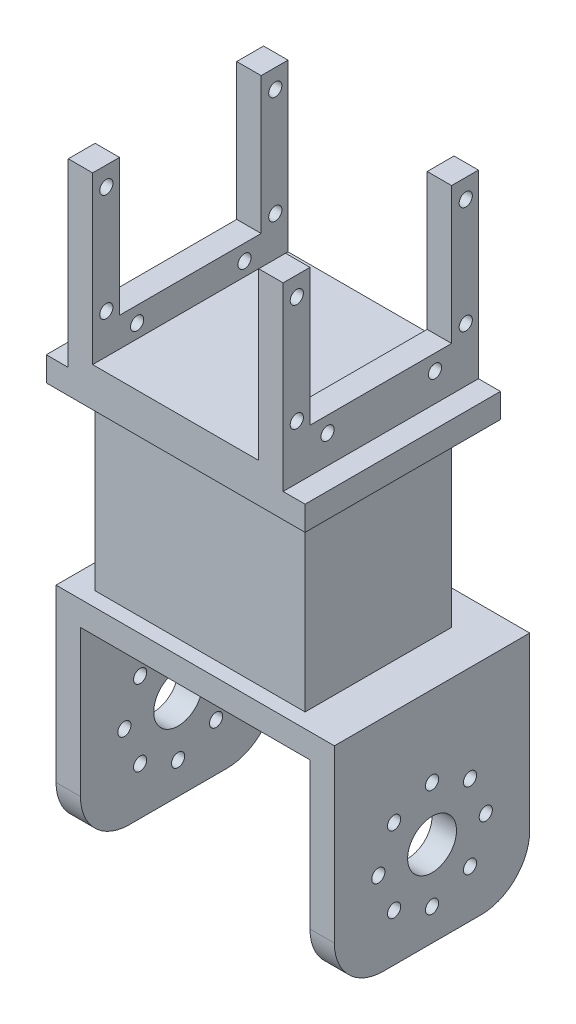
SolidWorks part; units mm, degrees
note: The reader was unsure of these and kept them because the rebuilt part matched: shared geometry of "Sketch8<3>".
material "Aluminium 1050"
ref_plane "Front Plane" through (0, 0, 0) normal (0, 0, 1) x (1, 0, 0)
ref_plane "Top Plane" through (0, 0, 0) normal (0, 1, 0) x (1, 0, 0)
ref_plane "Right Plane" through (0, 0, 0) normal (1, 0, 0) x (0, 0, -1)
sketch "Sketch2" plane through (0, 0, 0) normal (0, 1, 0) x (1, 0, 0)
  line L0 (0, 0) -> (34, 0)
  line L1 (34, 0) -> (34, 40)
  line L2 (34, 40) -> (0, 40)
  line L3 (0, 40) -> (0, 0)
  dimension "D1" = 34
  dimension "D2" = 40
extrude "Boss-Extrude1" add sketch "Sketch2" along normal blind 3
sketch "Sketch3" plane through (0, 0, 0) normal (0, 1, 0) x (1, 0, 0)
  line L0 (0, 0) -> (-5, 0)
  line L1 (-5, 0) -> (-5, 40)
  line L2 (-5, 40) -> (0, 40)
  line L3 (0, 40) -> (0, 0)
  line L4 (17, 40) -> (17, 0) construction
  line L5 (34, 40) -> (0, 40) construction
  line L6 (0, 0) -> (34, 0) construction
  line L7 (34, 40) -> (34, 0)
  line L8 (39, 40) -> (34, 40)
  line L9 (39, 0) -> (39, 40)
  line L10 (34, 0) -> (39, 0)
  dimension "D1" = 5
extrude "Boss-Extrude2" add sketch "Sketch3" along normal blind 37
sketch "Sketch4" plane through (-5, 0, 0) normal (-1, 0, 0) x (0, 0, 1)
  line L0 (-20, 37) -> (-20, 0) construction
  line L1 (-40, 37) -> (0, 37) construction
  line L2 (-40, 0) -> (0, 0) construction
  line L4 (-34.5, 9) -> (-5.5, 9)
  line L11 (-34.5, 37) -> (-34.5, 9)
  line L12 (-5.5, 37) -> (-5.5, 9)
  line L13 (-34.5, 37) -> (-5.5, 37)
  line L14 (-34.5, 37) -> (-34.5, 0) construction
  line L15 (-5.5, 37) -> (-5.5, 0) construction
  circle A2 centre (-2.8, 33.1) radius 1.35
  circle A3 centre (-2.8, 11.1) radius 1.35
  circle A4 centre (-9.1, 5.8) radius 1.35
  circle A5 centre (-37.4, 11.1) radius 1.35
  circle A6 centre (-31.1, 5.8) radius 1.35
  circle A7 centre (-37.4, 33.1) radius 1.35
  dimension "D1" = 2.7
  dimension "D2" = 2.7
  dimension "D3" = 2.7
  dimension "D4" = 2.7
  dimension "D5" = 2.7
  dimension "D6" = 2.7
  dimension "D7" = 14.5
  dimension "D8" = 14.5
  dimension "D9" = 28
extrude "Cut-Extrude1" cut sketch "Sketch4" against normal up to surface (44 mm away) up to face at (39, 18.5, -20)
sketch "Sketch5" plane through (0, 0, 0) normal (0, -1, 0) x (-1, 0, 0)
  line L0 (-17, 0) -> (-17, 40) construction
  line L1 (5, 0) -> (-39, 0) construction
  line L2 (-39, 40) -> (5, 40) construction
  line L3 (9.5, 0) -> (-43.5, 0)
  line L4 (-43.5, 0) -> (-43.5, 40)
  line L5 (-43.5, 40) -> (9.5, 40)
  line L6 (9.5, 0) -> (9.5, 40)
  dimension "D1" = 26.5
extrude "Boss-Extrude3" add sketch "Sketch5" along normal blind 5 contours L5 L6 L3 L4
sketch "Sketch6" plane through (0, -5, 0) normal (0, -1, 0) x (1, 0, 0)
  line L0 (-9.5, 0) -> (43.5, 0)
  line L1 (43.5, 0) -> (43.5, -40)
  line L2 (43.5, -40) -> (-9.5, -40)
  line L3 (-9.5, -40) -> (-9.5, 0)
  line L4 (-4.5, -35) -> (-4.5, -5)
  line L5 (-4.5, -5) -> (38.5, -5)
  line L6 (38.5, -5) -> (38.5, -35)
  line L7 (38.5, -35) -> (-4.5, -35)
  dimension "D1" = 5
extrude "Boss-Extrude4" add sketch "Sketch6" along normal blind 36.85 contours L4 L5 L6 L7
sketch "Sketch7" plane through (0, -41.85, 0) normal (0, -1, 0) x (1, 0, 0)
  line L0 (-7.5, -2) -> (45.5, -2)
  line L1 (45.5, -2) -> (45.5, -42)
  line L2 (45.5, -42) -> (-7.5, -42)
  line L3 (-7.5, -42) -> (-7.5, -2)
  line L4 (-4.5, -5) -> (38.5, -5) construction
  line L5 (-4.5, -35) -> (-4.5, -5) construction
  dimension "D1" = 40
  dimension "D2" = 53
  dimension "D3" = 3
  dimension "D4" = 3
extrude "Boss-Extrude5" add sketch "Sketch7" along normal blind 5
sketch "Sketch8" plane through (0, -46.85, 0) normal (0, -1, 0) x (1, 0, 0)
  line L0 (19, -2) -> (19, -42)
  line L1 (45.5, -2) -> (-7.5, -2) construction
  line L2 (-7.5, -42) -> (45.5, -42) construction
  line L3 (-4.5, -2) -> (-4.5, -42)
  line L4 (42.5, -2) -> (42.5, -42)
  line L5 (-9.5, -2) -> (-9.5, -42)
  line L6 (47.5, -2) -> (47.5, -42)
  line L7 (-9.5, -2) -> (-4.5, -2)
  line L8 (42.5, -2) -> (47.5, -2)
  line L9 (47.5, -42) -> (42.5, -42)
  line L10 (-4.5, -42) -> (-9.5, -42)
  line M1 (-7.5, -2) -> (-7.5, -42)
  line M2 (-7.5, -42) -> (45.5, -42)
  line M3 (45.5, -42) -> (45.5, -2)
  line M4 (45.5, -2) -> (-7.5, -2)
  dimension "D1" = 23.5
  dimension "D2" = 23.5
  dimension "D3" = 28.5
  dimension "D4" = 28.5
extrude "Boss-Extrude6" add sketch "Sketch8" along normal blind 40 contours L10 L7 L5 M1 | L3 M4 M1 M2 | L9 L6 L8 M3
extrude "Boss-Extrude7" add sketch "Sketch8<3>" against normal up to surface (5 mm away) contours L9 L6 L8 M3 | L10 L7 L5 M1 up to face at (19, -41.85, -22)
sketch "Sketch8<3>" plane through (0, -46.85, 0) normal (0, -1, 0) x (1, 0, 0) same geometry as "Sketch8"
sketch "Sketch9" plane through (0, 0, 0) normal (-1, 0, 0) x (0, 0, 1)
  line L0 (-42, -46.85) -> (-2, -46.85)
  line L1 (-42, -69.35) -> (-2, -69.35) construction
  line L5 (-2, -46.85) -> (-2, -76.85)
  line L6 (-12, -86.85) -> (-32, -86.85)
  line L7 (-42, -76.85) -> (-42, -46.85)
  line L8 (-2, -46.85) -> (-42, -46.85)
  line L9 (-2, -76.85) -> (-2, -86.85)
  line L10 (-2, -86.85) -> (-12, -86.85)
  line L11 (-32, -86.85) -> (-42, -86.85)
  line L12 (-42, -86.85) -> (-42, -76.85)
  circle A0 centre (-22, -69.35) radius 5
  circle A1 centre (-22, -69.35) radius 11 construction
  circle A2 centre (-22, -58.35) radius 1.35
  circle A3 centre (-14.2218, -61.5718) radius 1.35
  circle A4 centre (-22, -69.35) radius 11 construction
  circle A5 centre (-11, -69.35) radius 1.35
  circle A6 centre (-22, -69.35) radius 11 construction
  circle A7 centre (-14.2218, -77.1282) radius 1.35
  circle A8 centre (-22, -69.35) radius 11 construction
  circle A9 centre (-22, -80.35) radius 1.35
  circle A10 centre (-22, -69.35) radius 11 construction
  circle A11 centre (-29.7782, -77.1282) radius 1.35
  circle A12 centre (-22, -69.35) radius 11 construction
  circle A13 centre (-33, -69.35) radius 1.35
  circle A14 centre (-22, -69.35) radius 11 construction
  circle A15 centre (-29.7782, -61.5718) radius 1.35
  circle A16 centre (-22, -69.35) radius 11 construction
  arc A19 (-32, -86.85) -> (-42, -76.85) centre (-32, -76.85) cw
  arc A20 (-12, -86.85) -> (-2, -76.85) centre (-12, -76.85) ccw
  point P34 (-22, -69.35)
  point P39 (-42, -86.85)
  point P42 (-2, -86.85)
  dimension "D2" = 10
  dimension "D3" = 22
  dimension "D4" = 2.7
  dimension "D6" = 10
  dimension "D1" = 22.5
  dimension "D5" = 8
extrude "Cut-Extrude2" cut sketch "Sketch9" against normal through all both and the other way through all contours L10 A20 L9 | A19 L11 L12 | A7 | A9 | A11 | A15 | A13 | A0 | A5 | A3 | A2
